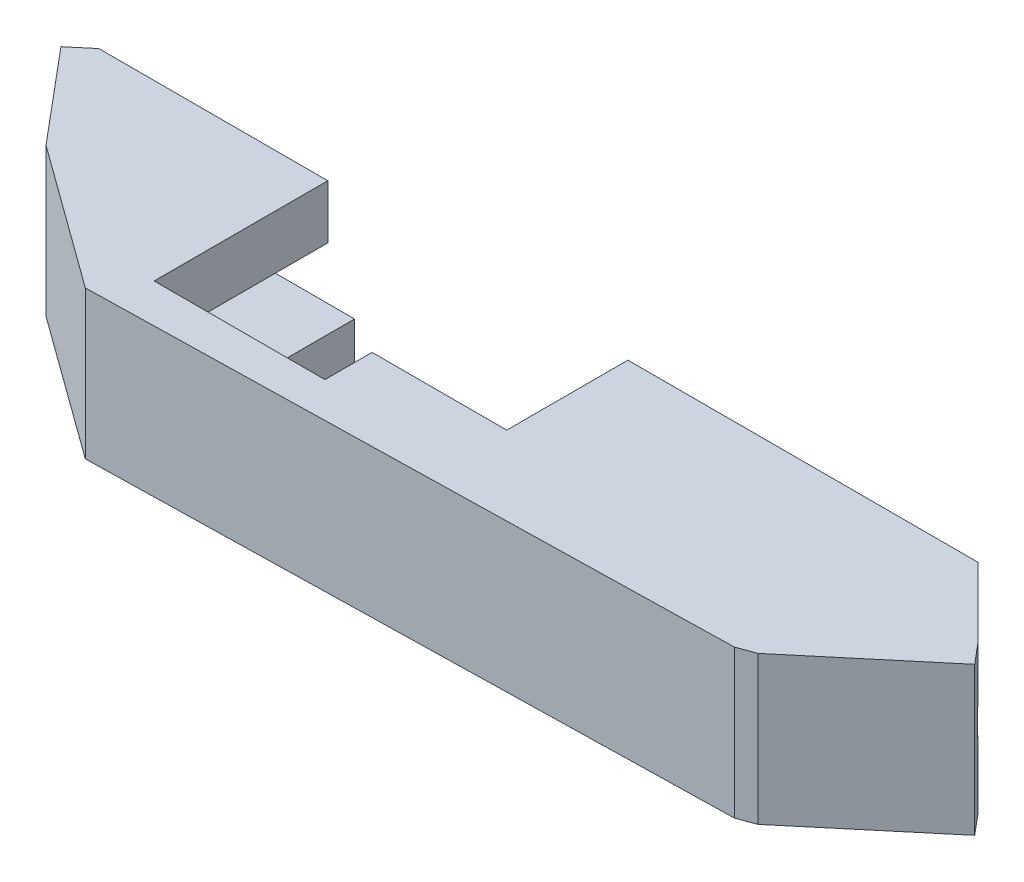
SolidWorks part; units mm, degrees
ref_plane "Front Plane" through (0, 0, 0) normal (0, 0, 1) x (1, 0, 0)
ref_plane "Top Plane" through (0, 0, 0) normal (0, 1, 0) x (1, 0, 0)
ref_plane "Right Plane" through (0, 0, 0) normal (1, 0, 0) x (0, 0, -1)
sketch "Sketch1" plane through (0, 0, 0) normal (0, 1, 0) x (1, 0, 0)
  line L0 (0, 0) -> (28.8, 0)
  line L1 (0, 0) -> (0, 6)
  line L2 (0, 6) -> (-9.1, 6)
  line L3 (0, 6) -> (-2.3, 6)
  line L4 (0, 6) -> (0, 3.7)
  line L5 (39.0587, 0) -> (39.1, 0)
  line L6 (33.95, 4.4993) -> (33.95, 4.1993)
  line L7 (-9.1, 6) -> (-14.8851, 12.8944)
  line L8 (28.8, 0) -> (28.8413, 0)
  line L9 (39.1, 0) -> (47.2, 0)
  line L10 (47.2, 0) -> (55.9543, 7.3457)
  line L11 (33.95, 4.4993) -> (33.95, 5.15)
  line L12 (33.95, 0) -> (33.95, -0.65)
  line L13 (-14.8851, 12.8944) -> (2.1149, 12.8944)
  line L14 (2.1149, 12.8944) -> (2.1149, 0)
  line L15 (28.8, 0) -> (24.8, 0)
  line L16 (24.8, 3.5) -> (24.8, 12.5)
  line L17 (24.8, 12.5) -> (50.8, 12.5)
  line L18 (0, 0) -> (0, -0.3)
  line L19 (50.8, 12.5) -> (55.9543, 7.3457)
  line L20 (24.8, 0) -> (14.8, 0)
  line L21 (14.8, 0) -> (14.8, 3.5)
  line L22 (14.8, 3.5) -> (24.8, 3.5)
  line L23 (0, -0.3) -> (47.2, -0.3)
  line L24 (28.8413, 0) -> (28.8885, 0)
  line L25 (-10.6321, 4.7144) -> (-16.4172, 11.6088)
  line L26 (-14.8851, 12.8944) -> (-16.4172, 11.6088)
  line L27 (0, 0) -> (0, -3)
  line L28 (-10.6321, 4.7144) -> (0, -3)
  line L29 (47.2, 0) -> (47.2, -0.3)
  line L30 (47.2, 0) -> (47.3928, -0.2298)
  line L31 (48.4856, -1.5321) -> (57.2399, 5.8136)
  line L32 (55.9543, 7.3457) -> (57.2399, 5.8136)
  line L33 (47.2, -2) -> (48.4856, -1.5321)
  line L34 (0, -3) -> (47.2, -2)
  line L35 (55.9543, 7.3457) -> (56.1471, 7.1159)
  line L36 (56.1471, 7.1159) -> (47.3092, -0.3)
  line L37 (47.2, -0.3) -> (47.3092, -0.3)
  line L38 (47.4517, -0.3) -> (48.4856, -1.5321)
  line L39 (0, 0) -> (-0.3, 0)
  line L40 (-0.3, 0) -> (-0.3, 4.1175)
  line L41 (-0.3, 0) -> (-0.3, -0.3)
  line L42 (0, -0.3) -> (-0.3, -0.3)
  line L43 (-0.3, 3.7) -> (-2.3, 3.7)
  line L44 (-2.3, 3.7) -> (-2.5121, 3.4879)
  line L45 (-2.3, 3.7) -> (-0.8858, 5.1142)
  line L46 (-2.5121, 3.4879) -> (-0.8858, 5.1142)
  line L47 (28.8413, -0.3) -> (29.0413, -0.3)
  line L48 (-9.1, 5.7) -> (-1.8825, 5.7)
  line L49 (-14.8851, 12.8944) -> (-15.1149, 12.7016)
  line L50 (-15.1149, 12.7016) -> (-9.2399, 5.7)
  line L51 (-9.1, 5.7) -> (-9.2399, 5.7)
  line L52 (29.0413, -0.3) -> (29.0413, 0.6071)
  line L53 (39.0587, -0.3) -> (38.8587, -0.3)
  line L54 (38.8587, -0.3) -> (38.8587, 0.6071)
  arc A0 (0, 3.7) -> (-2.3, 6) centre (-2.3, 3.7) ccw
  arc A1 (39.0587, 0) -> (28.8413, 0) centre (33.95, -0.6507) ccw
  arc A2 (39.0587, -0.3) -> (28.8413, -0.3) centre (33.95, -0.9507) ccw
  arc A3 (-0.3, 4.1175) -> (-1.8825, 5.7) centre (-2.5121, 3.4879) ccw
  dimension "D1" = 28.8
  dimension "D2" = 6
  dimension "D3" = 9.1
  dimension "D4" = 2.3
  dimension "D5" = 2.3
  dimension "D6" = 9
  dimension "D7" = 10.3
  dimension "D8" = 8.1
  dimension "D9" = 130
  dimension "D10" = 140
  dimension "D11" = 5.15
  dimension "D12" = 0.65
  dimension "D13" = 17
  dimension "D14" = 4
  dimension "D15" = 12.5
  dimension "D16" = 26
  dimension "D17" = 0.3
  dimension "D18" = 10
  dimension "D19" = 3.5
  dimension "D20" = 2
  dimension "D21" = 0.2
  dimension "D22" = 3
  dimension "D23" = 2
  dimension "D24" = 90
  dimension "D25" = 2
  dimension "D26" = 2
  dimension "D27" = 0.3
  dimension "D28" = 90
  dimension "D29" = 0.3
  dimension "D30" = 0.3
  dimension "D31" = 45
  dimension "D32" = 0.3
  dimension "D33" = 0.3
  dimension "D34" = 90
  dimension "D35" = 0.2
extrude "Boss-Extrude1" add sketch "Sketch1" along normal blind 4 contours A1 L5 L9 L10 L19 L17 L16 L22 L21 L0 L8 | A2 L6 A1 L24 | L54 A2 L52 L23 | A2 L23 L29 L9 L5 A1 L6 | L23 A2 L54 | L37 L23 L27 L34 L33 L31 L32 L36 | L36 L32 L10 L30 | A2 L24 L8 L0 L18 L23 | L52 A2 L23 | L14 L13 L7 L2 L1 L0 | A3 L40 L39 L1 A0 L2 L7 L26 L50 L51 L48 | L45 A3 L48 L51 L50 L26 L25 L28 L27 L42 L41 L40 L43 | A0 L1 L2 | L40 A3 L45 L43 region at (-4.3342, 0, -8.9115) region at (-0.15, 0, -0.1987) region at (14.4317, 0, 0.15) region at (-0.5137, 0, -5.4863) region at (26.8312, 0, 0.7598) region at (-6.2822, 0, -4.141) region at (37.2188, 0, -6.4157) region at (28.9694, 0, -0.0216) region at (-1.0895, 0, -4.1985) region at (33.95, 0, -1.6) region at (28.8649, 0, -0.0681) region at (38.9306, 0, -0.0216) region at (34.0909, 0, -4.3493) region at (51.6736, 0, -3.558)
extrude "Boss-Extrude2" add sketch "Sketch1<5>" along normal blind 4 contours L42 L18 L39 L41 | L29 L37 L36 L30 region at (-0.15, 0, 0.15) region at (47.2685, 0, 0.1883)
sketch "Sketch1<5>" plane through (0, 0, 0) normal (0, 1, 0) x (1, 0, 0) same geometry as "Sketch1"
extrude "Boss-Extrude3" add sketch "Sketch1<6>" against normal blind 3 contours L37 L23 L27 L34 L33 L31 L32 L36 | L45 A3 L48 L51 L50 L26 L25 L28 L27 L42 L41 L40 L43 | L40 A3 L45 L43 | L54 A2 L52 L23 region at (26.8312, 0, 0.7598) region at (-6.2822, 0, -4.141) region at (-1.0895, 0, -4.1985) region at (33.95, 0, -1.6)
sketch "Sketch1<6>" plane through (0, 0, 0) normal (0, 1, 0) x (1, 0, 0) same geometry as "Sketch1"
ref_plane "Plane1" through (0, -3, 0) normal (0, -1, 0) x (-1, 0, 0)
sketch "Sketch2" plane through (0, -3, 0) normal (0, -1, 0) x (-1, 0, 0)
  line L0 (-47.2, 0) -> (-51.7963, 3.8567)
  line L1 (-51.7963, 3.8567) -> (-51.7963, 10.5333)
  line L2 (-28.8413, 0) -> (-21.2104, 0)
  line L6 (-21.8, 5.0006) -> (-21.8, 11)
  line L7 (-21.8, 11) -> (-51.7963, 11)
  line L11 (-51.7963, 10.5333) -> (-51.7963, 11)
  line L12 (0, 0) -> (-6, 0)
  line L13 (-6, 4.9401) -> (-6, 11)
  line L14 (-6, 11) -> (13.2955, 11)
  line L24 (-21.8, 5.0006) -> (-6, 5.0006)
  line L55 (-21.8, 0) -> (-21.8, -0.3)
  line L56 (-38.8587, -0.3) -> (-38.8587, 0.6071)
  line L57 (-39.0587, -0.3) -> (-38.8587, -0.3)
  line L58 (-29.0413, -0.3) -> (-29.0413, 0.6071)
  line L59 (9.1, 5.7) -> (9.2399, 5.7)
  line L60 (15.1149, 12.7016) -> (9.2399, 5.7)
  line L61 (14.8851, 12.8944) -> (15.1149, 12.7016)
  line L62 (9.1, 5.7) -> (1.8825, 5.7)
  line L63 (-28.8413, -0.3) -> (-29.0413, -0.3)
  line L64 (2.5121, 3.4879) -> (0.8858, 5.1142)
  line L65 (2.3, 3.7) -> (0.8858, 5.1142)
  line L66 (2.3, 3.7) -> (2.5121, 3.4879)
  line L67 (0.3, 3.7) -> (2.3, 3.7)
  line L68 (0, -0.3) -> (0.3, -0.3)
  line L69 (0.3, 0) -> (0.3, -0.3)
  line L70 (0.3, 0) -> (0.3, 4.1175)
  line L71 (0, 0) -> (0.3, 0)
  line L72 (-47.4517, -0.3) -> (-48.4856, -1.5321)
  line L73 (-47.2, -0.3) -> (-47.3092, -0.3)
  line L74 (-56.1471, 7.1159) -> (-47.3092, -0.3)
  line L75 (-55.9543, 7.3457) -> (-56.1471, 7.1159)
  line L76 (0, -3) -> (-47.2, -2)
  line L77 (-47.2, -2) -> (-48.4856, -1.5321)
  line L78 (-55.9543, 7.3457) -> (-57.2399, 5.8136)
  line L79 (-48.4856, -1.5321) -> (-57.2399, 5.8136)
  line L80 (-47.2, 0) -> (-47.3928, -0.2298)
  line L81 (-47.2, 0) -> (-47.2, -0.3)
  line L82 (10.6321, 4.7144) -> (0, -3)
  line L83 (0, 0) -> (0, -3)
  line L84 (14.8851, 12.8944) -> (16.4172, 11.6088)
  line L85 (10.6321, 4.7144) -> (16.4172, 11.6088)
  line L86 (-28.8413, 0) -> (-28.8885, 0)
  line L87 (0, -0.3) -> (-47.2, -0.3)
  line L89 (-14.8, 0) -> (-14.8, 3.5)
  line L90 (-24.8, 0) -> (-14.8, 0)
  line L91 (-50.8, 12.5) -> (-55.9543, 7.3457)
  line L92 (0, 0) -> (0, -0.3)
  line L93 (-24.8, 12.5) -> (-50.8, 12.5)
  line L94 (-24.8, 11) -> (-24.8, 12.5)
  line L95 (-28.8, 0) -> (-24.8, 0)
  line L96 (-2.1149, 12.8944) -> (-2.1149, 0)
  line L97 (14.8851, 12.8944) -> (-2.1149, 12.8944)
  line L98 (-33.95, 0) -> (-33.95, -0.65)
  line L100 (-47.2, 0) -> (-55.9543, 7.3457)
  line L101 (-39.1, 0) -> (-47.2, 0)
  line L102 (-28.8, 0) -> (-28.8413, 0)
  line L103 (9.1, 6) -> (14.8851, 12.8944)
  line L104 (-33.95, 4.4993) -> (-33.95, 4.1993)
  line L105 (-39.0587, 0) -> (-39.1, 0)
  line L106 (0, 6) -> (0, 3.7)
  line L107 (0, 6) -> (2.3, 6)
  line L108 (0, 6) -> (9.1, 6)
  line L109 (0, 0) -> (0, 6)
  line L110 (0, 0) -> (-28.8, 0)
  arc A4 (0.3, 4.1175) -> (1.8825, 5.7) centre (2.5121, 3.4879) cw
  arc A5 (-39.0587, -0.3) -> (-28.8413, -0.3) centre (-33.95, -0.9507) cw
  arc A6 (-39.0587, 0) -> (-28.8413, 0) centre (-33.95, -0.6507) cw
  arc A7 (0, 3.7) -> (2.3, 6) centre (2.3, 3.7) cw
  dimension "D1" = 6
  dimension "D2" = 7
  dimension "D3" = 11
  dimension "D4" = 6
extrude "Boss-Extrude4" add sketch "Sketch2" along normal blind 4 and the other way blind 0.998 contours A6 L2 L90 L110 L12 L96 L14 L13 L24 L6 L7 L11 L1 L0 L101 L105 | L83 L87 L63 L57 L73 L74 L78 L79 L77 L76 | L0 L100 L75 L74 L80 | A6 L105 L101 L81 L87 A5 L104 | A5 L57 L56 | A5 L56 L87 L58 | A6 L104 A5 L86 | A5 L58 L63 | L86 A5 L87 L55 L2 | L12 L110 L90 L2 L55 L87 L83 | L12 L109 L106 L107 L108 L103 L14 L96 | A4 L64 L67 L70 L69 L68 L83 L82 L85 L84 L60 L59 L62 | A7 L109 L71 L70 A4 L62 L59 L60 L61 L103 L108 | A4 L70 L67 L64 | L106 A7 L107 | L71 L83 L68 L69 | L81 L80 L74 L73 region at (51.6736, -3, -3.558) region at (47.2685, -3, 0.1883) region at (43.15, -3, 0.1409) region at (28.8835, -3, -5.32) region at (26.8312, -3, 0.7598) region at (38.9306, -3, -0.0216) region at (33.95, -3, -1.6) region at (30.5912, -3, -3.163) region at (25.3317, -3, 0.1498) region at (28.9694, -3, -0.0216) region at (-6.2822, -3, -4.141) region at (-0.15, -3, 0.15) region at (10.9, -3, 0.15) region at (-0.1987, -3, -1.85) region at (-3.6912, -3, -7.7297) region at (-0.5137, -3, -5.4863) region at (-1.0895, -3, -4.1985)
